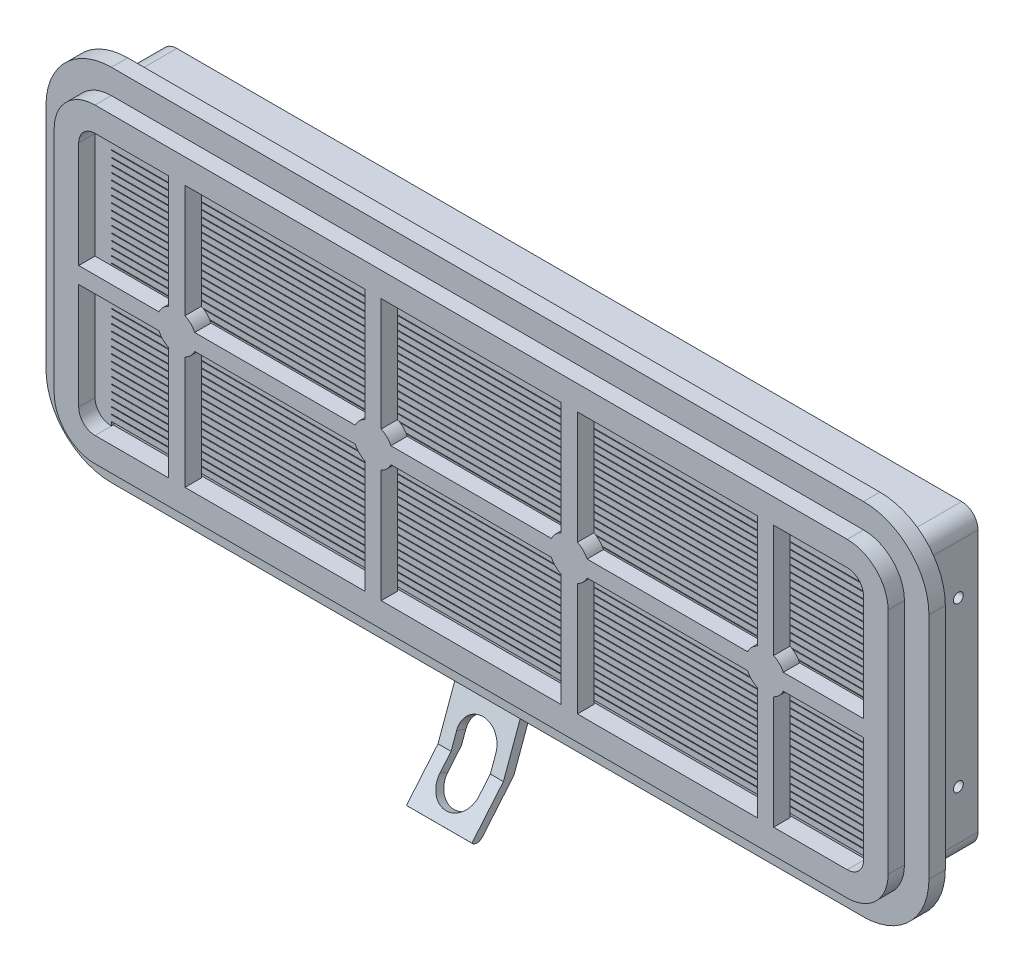
SolidWorks part; units mm, degrees
ref_plane "Plan de face" through (0, 0, 0) normal (0, 0, 1) x (1, 0, 0)
ref_plane "Plan de dessus" through (0, 0, 0) normal (0, 1, 0) x (1, 0, 0)
ref_plane "Plan de droite" through (0, 0, 0) normal (1, 0, 0) x (0, 0, -1)
sketch "Esquisse1" plane through (0, 0, 0) normal (0, 0, 1) x (1, 0, 0)
  line L0 (-115, 40) -> (115, 40)
  line L1 (-120, 45) -> (120, 45)
  line L2 (-125, 40) -> (-125, -40)
  line L3 (-120, -45) -> (120, -45)
  line L4 (125, 40) -> (125, -40)
  line L5 (-125, 45) -> (125, -45) construction
  line L6 (-125, -45) -> (125, 45) construction
  line L7 (120, 35) -> (120, -35)
  line L8 (-115, -40) -> (115, -40)
  line L9 (-120, 35) -> (-120, -35)
  line L10 (-125, -45) -> (125, -45) construction
  line L11 (125, 45) -> (125, -45) construction
  line L12 (120, 40) -> (120, -40) construction
  line L13 (-120, -40) -> (120, -40) construction
  line L14 (-125, 45) -> (125, 45) construction
  line L15 (-120, 40) -> (120, 40) construction
  line L16 (-120, 40) -> (-120, -40) construction
  line L17 (-125, 45) -> (-125, -45) construction
  arc A0 (120, -45) -> (125, -40) centre (120, -40) ccw
  arc A1 (120, -35) -> (115, -40) centre (115, -35) cw
  arc A2 (120, 45) -> (125, 40) centre (120, 40) cw
  arc A3 (115, 40) -> (120, 35) centre (115, 35) cw
  arc A4 (-115, -40) -> (-120, -35) centre (-115, -35) cw
  arc A5 (-125, -40) -> (-120, -45) centre (-120, -40) ccw
  arc A6 (-115, 40) -> (-120, 35) centre (-115, 35) ccw
  arc A7 (-120, 45) -> (-125, 40) centre (-120, 40) ccw
  point P0 (0, 0)
  dimension "D4" = 5
  dimension "D1" = 250
  dimension "D2" = 90
  dimension "D3" = 5
extrude "Boss.-Extru.1" add sketch "Esquisse1" along normal blind 50
sketch "Esquisse2" plane through (0, 0, 50) normal (0, 0, 1) x (1, 0, 0)
  line L0 (-115, -40) -> (115, -40) construction
  line L1 (120, -35) -> (120, 35) construction
  line L2 (115, 40) -> (-115, 40) construction
  line L3 (-120, 35) -> (-120, -35) construction
  line L4 (-115, -40) -> (115, -40)
  line L5 (120, -35) -> (120, 35)
  line L6 (115, 40) -> (-115, 40)
  line L7 (-120, 35) -> (-120, -35)
  line L8 (-115, -55) -> (115, -55)
  line L9 (135, -35) -> (135, 35)
  line L10 (115, 55) -> (-115, 55)
  line L11 (-135, 35) -> (-135, -35)
  arc A0 (-120, -35) -> (-115, -40) centre (-115, -35) ccw construction
  arc A1 (115, -40) -> (120, -35) centre (115, -35) ccw construction
  arc A2 (120, 35) -> (115, 40) centre (115, 35) ccw construction
  arc A3 (-115, 40) -> (-120, 35) centre (-115, 35) ccw construction
  arc A4 (-120, -35) -> (-115, -40) centre (-115, -35) ccw
  arc A5 (115, -40) -> (120, -35) centre (115, -35) ccw
  arc A6 (120, 35) -> (115, 40) centre (115, 35) ccw
  arc A7 (-115, 40) -> (-120, 35) centre (-115, 35) ccw
  arc A8 (-135, -35) -> (-115, -55) centre (-115, -35) ccw
  arc A9 (115, -55) -> (135, -35) centre (115, -35) ccw
  arc A10 (135, 35) -> (115, 55) centre (115, 35) ccw
  arc A11 (-115, 55) -> (-135, 35) centre (-115, 35) ccw
  dimension "D1" = 15
extrude "Boss.-Extru.3" add sketch "Esquisse2" along normal blind 5
sketch "Esquisse3" plane through (0, 0, 55) normal (0, 0, 1) x (1, 0, 0)
  line L0 (-120, 35) -> (-120, -35) construction
  line L1 (-120, 35) -> (-120, -35)
  line L2 (-115, -40) -> (115, -40) construction
  line L3 (120, -35) -> (120, 35) construction
  line L4 (115, 40) -> (-115, 40) construction
  line L5 (-115, -40) -> (115, -40)
  line L6 (120, -35) -> (120, 35)
  line L7 (115, 40) -> (-115, 40)
  line L8 (-127.5, 35) -> (-127.5, -35)
  line L9 (-115, -47.5) -> (115, -47.5)
  line L10 (127.5, -35) -> (127.5, 35)
  line L11 (115, 47.5) -> (-115, 47.5)
  arc A0 (-120, -35) -> (-115, -40) centre (-115, -35) ccw construction
  arc A1 (115, -40) -> (120, -35) centre (115, -35) ccw construction
  arc A2 (120, 35) -> (115, 40) centre (115, 35) ccw construction
  arc A3 (-115, 40) -> (-120, 35) centre (-115, 35) ccw construction
  arc A4 (-120, -35) -> (-115, -40) centre (-115, -35) ccw
  arc A5 (115, -40) -> (120, -35) centre (115, -35) ccw
  arc A6 (120, 35) -> (115, 40) centre (115, 35) ccw
  arc A7 (-115, 40) -> (-120, 35) centre (-115, 35) ccw
  arc A8 (-127.5, -35) -> (-115, -47.5) centre (-115, -35) ccw
  arc A9 (115, -47.5) -> (127.5, -35) centre (115, -35) ccw
  arc A10 (127.5, 35) -> (115, 47.5) centre (115, 35) ccw
  arc A11 (-115, 47.5) -> (-127.5, 35) centre (-115, 35) ccw
  dimension "D1" = 7.5
extrude "Boss.-Extru.4" add sketch "Esquisse3" along normal blind 5
sketch "Esquisse4" plane through (0, 0, 60) normal (0, 0, 1) x (1, 0, 0)
  line L0 (-180.9015, 0) -> (181.7643, 0) construction
  line L1 (-120, -2.5) -> (120, -2.5)
  line L2 (-120, 35) -> (-120, -35) construction
  line L3 (120, -35) -> (120, 35) construction
  line L4 (-127.5, 35) -> (-127.5, -35)
  line L5 (-115, -47.5) -> (115, -47.5)
  line L6 (127.5, -35) -> (127.5, 35)
  line L7 (115, 47.5) -> (-115, 47.5)
  line L8 (-127.5, 35) -> (-127.5, -35)
  line L9 (-115, -47.5) -> (115, -47.5)
  line L10 (127.5, -35) -> (127.5, 35)
  line L11 (115, 47.5) -> (-115, 47.5)
  line L12 (-120, 2.5) -> (120, 2.5)
  line L13 (-92.5, 40) -> (-92.5, -40)
  line L14 (-115, -40) -> (115, -40)
  line L15 (115, 40) -> (-115, 40)
  line L16 (-90, 75.1442) -> (-90, -69.1311) construction
  line L17 (115, 40) -> (-115, 40) construction
  line L18 (-115, -40) -> (115, -40) construction
  line L19 (-87.5, 40) -> (-87.5, -40)
  line L20 (-32.5, 40) -> (-32.5, -40)
  line L21 (-27.5, 40) -> (-27.5, -40)
  line L22 (27.5, 40) -> (27.5, -40)
  line L23 (32.5, 40) -> (32.5, -40)
  line L24 (87.5, 40) -> (87.5, -40)
  line L25 (92.5, 40) -> (92.5, -40)
  line L26 (120, -35) -> (120, 35)
  line L27 (-120, 35) -> (-120, -35)
  circle A0 centre (-90, 0) radius 6
  circle A1 centre (-30, 0) radius 6
  circle A2 centre (30, 0) radius 6
  circle A3 centre (90, 0) radius 6
  arc A4 (-115, 47.5) -> (-127.5, 35) centre (-115, 35) ccw
  arc A5 (-127.5, -35) -> (-115, -47.5) centre (-115, -35) ccw
  arc A6 (115, -47.5) -> (127.5, -35) centre (115, -35) ccw
  arc A7 (127.5, 35) -> (115, 47.5) centre (115, 35) ccw
  arc A8 (-115, 47.5) -> (-127.5, 35) centre (-115, 35) ccw
  arc A9 (-127.5, -35) -> (-115, -47.5) centre (-115, -35) ccw
  arc A10 (115, -47.5) -> (127.5, -35) centre (115, -35) ccw
  arc A11 (127.5, 35) -> (115, 47.5) centre (115, 35) ccw
  line M32 (-115, 40) -> (115, 40)
  dimension "D6" = 12
  dimension "D2" = 2.5
  dimension "D3" = 30
  dimension "D4" = 2.5
  dimension "D1" = 0
  dimension "D5" = 4
  dimension "D7" = 4
extrude "Boss.-Extru.5" add sketch "Esquisse4" against normal blind 5 contours A0 L19 L13 M32 | L19 A0 L13 L12 | L1 A0 L12 L19 | L12 A0 L19 | L19 L12 L13 L1 | L13 A0 L12 | L12 A0 L1 L13 | L13 A0 L19 L1 | L1 A0 L13 | L19 A0 L1 | A0 L13 L14 L19 region at (-94.1647, 0, 60) region at (-93.6011, -3.6011, 60) region at (-90, 0, 60) region at (-90, -4.1647, 60) region at (-93.6011, 3.6011, 60) region at (-90, -22.9104, 60) region at (-85.8353, 0, 60) region at (-86.3989, -3.6011, 60) region at (-90, 4.1647, 60) region at (-90, 22.9104, 60) region at (-86.3989, 3.6011, 60)
pattern_linear "Répétition linéaire1" count 4 spacing 60 along (1, 0, 0) of "Boss.-Extru.5"
sketch "Esquisse5" plane through (0, 0, 60) normal (0, 0, 1) x (1, 0, 0)
  line L0 (-163.933, 0) -> (179.1758, 0) construction
  line L1 (-120, 2.5) -> (120, 2.5)
  line L2 (-120, 35) -> (-120, -35) construction
  line L3 (120, -35) -> (120, 35) construction
  line L4 (-120, -2.5) -> (120, -2.5)
  line L5 (-120, 2.5) -> (-120, -2.5)
  line L6 (120, -2.5) -> (120, 2.5)
  dimension "D1" = 2.5
extrude "Boss.-Extru.6" add sketch "Esquisse5" against normal blind 5
sketch "Esquisse9" plane through (0, 0, 0) normal (1, 0, 0) x (0, 0, -1)
  line L0 (-55, -55) -> (-60.1303, -69.0954)
  line L1 (-55, -35) -> (-55, -55) construction
  line L2 (-51.596, -54.4191) -> (-56.9378, -69.0954)
  line L3 (-60.1303, -69.0954) -> (-69.7721, -80.5861)
  line L4 (-56.9378, -69.0954) -> (-66.5796, -80.5861)
  line L5 (-55, -55) -> (-51.596, -54.4191)
  arc A0 (-69.7721, -80.5861) -> (-66.5796, -80.5861) centre (-68.1758, -79.2466) ccw
  dimension "D1" = 15
  dimension "D2" = 160
  dimension "D3" = 3
  dimension "D4" = 160
  dimension "D5" = 15
extrude "Boss.-Extru.8" add sketch "Esquisse9" along normal blind 10 and the other way blind 10
ref_plane "Plan1" through (0, 14.6631, 40.2865) normal (0, 0.342, 0.9397) x (1, 0, 0)
sketch "Esquisse10" plane through (0, 14.6631, 40.2865) normal (0, 0.342, 0.9397) x (1, 0, 0)
  line L0 (-10, -85.4942) -> (10, -85.4942) construction
  line L1 (-10, -85.4942) -> (10, -85.4942)
  line L2 (0, -80.4942) -> (0, -90.4942) construction
  line L3 (6, -80.4942) -> (6, -90.4942)
  line L4 (-6, -80.4942) -> (-6, -90.4942)
  arc A0 (6, -80.4942) -> (-6, -80.4942) centre (0, -80.4942) ccw
  arc A1 (-6, -90.4942) -> (6, -90.4942) centre (0, -90.4942) ccw
  point P5 (0, -85.4942)
  dimension "D2" = 6
  dimension "D1" = 10
extrude "Enlèv. mat.-Extru.1" cut sketch "Esquisse10" against normal through all contours L3 A0 L4 L1 | L4 A1 L3 L1 region at (0, -61.0251, 67.8347) region at (0, -70.3253, 71.2197)
ref_plane "Plan2" through (115, 0, 0) normal (-1, 0, 0) x (0, 0, 1)
sketch "Esquisse11" plane through (115, 0, 0) normal (-1, 0, 0) x (0, 0, 1)
  line L0 (60, 35) -> (0, 35) construction
  line L1 (60, 35) -> (0, 35)
  line L2 (54.5087, 34.5001) -> (46.5299, 34.3608)
  line L3 (46.5299, 34.3608) -> (46.5299, 32.1863) construction
  line L4 (55.104, 34.1108) -> (42.39, 34.1108) construction
  line L5 (54.5087, 33.7216) -> (46.5299, 33.8609)
  line L6 (55, 35) -> (55, 33.2217)
  arc A0 (55, 35) -> (54.5087, 34.5001) centre (54.5, 35) cw
  arc A1 (46.5299, 34.3608) -> (46.5299, 33.8609) centre (46.5343, 34.1108) ccw
  arc A2 (55, 33.2217) -> (54.5087, 33.7216) centre (54.5, 33.2217) ccw
  dimension "D1" = 0.5
  dimension "D3" = 0.25
  dimension "D2" = 1
extrude "Boss.-Extru.9" add sketch "Esquisse11" along normal blind 230 contours A2 L6 A0 L2 A1 L5 region at (115, 34.1108, 51.0774)
pattern_linear "Répétition linéaire2" count 37 spacing 2 along (0, -1, 0) of "Boss.-Extru.9"
sketch "Esquisse12" plane through (-115, 0, 0) normal (-1, 0, 0) x (0, 0, 1)
  line L0 (55, -37) -> (55, -38.7783) construction
  line L1 (55, -37) -> (55, -38.7783)
  line L2 (55, 35) -> (55, 33.2217) construction
  line L3 (55, 35) -> (55, 33.2217)
  line L4 (60, -40) -> (0, -40) construction
  line L5 (60, -40) -> (40, -40)
  line L6 (60, 40) -> (0, 40) construction
  line L7 (60, 40) -> (40, 40)
  line L9 (60, -40) -> (40, -40)
  line L10 (60, -40) -> (60, 40)
  line L11 (60, 40) -> (40, 40)
  line L12 (40, -40) -> (40, 40)
  dimension "D1" = 20
extrude "Extru.-Mince1" add sketch "Esquisse12" along normal blind 5 thin contours L12 thin type one direction wall 10
sketch "Esquisse13" plane through (0, 0, 50) normal (0, 0, 1) x (1, 0, 0)
  line L76 (-120, 35) -> (-120, -35)
  line L77 (-115, -40) -> (-115, -38.1997)
  line L78 (-115, -38.1997) -> (-115, -37.5786)
  line L79 (-115, -37.5786) -> (-115, -36.1997)
  line L80 (-115, -36.1997) -> (-115, -35.5786)
  line L81 (-115, -35.5786) -> (-115, -34.1997)
  line L82 (-115, -34.1997) -> (-115, -33.5786)
  line L83 (-115, -33.5786) -> (-115, -32.1997)
  line L84 (-115, -32.1997) -> (-115, -31.5786)
  line L85 (-115, -31.5786) -> (-115, -30.1997)
  line L86 (-115, -30.1997) -> (-115, -29.5786)
  line L87 (-115, -29.5786) -> (-115, -28.1997)
  line L88 (-115, -28.1997) -> (-115, -27.5786)
  line L89 (-115, -27.5786) -> (-115, -26.1997)
  line L90 (-115, -26.1997) -> (-115, -25.5786)
  line L91 (-115, -25.5786) -> (-115, -24.1997)
  line L92 (-115, -24.1997) -> (-115, -23.5786)
  line L93 (-115, -23.5786) -> (-115, -22.1997)
  line L94 (-115, -22.1997) -> (-115, -21.5786)
  line L95 (-115, -21.5786) -> (-115, -20.1997)
  line L96 (-115, -20.1997) -> (-115, -19.5786)
  line L97 (-115, -19.5786) -> (-115, -18.1997)
  line L98 (-115, -18.1997) -> (-115, -17.5786)
  line L99 (-115, -17.5786) -> (-115, -16.1997)
  line L100 (-115, -16.1997) -> (-115, -15.5786)
  line L101 (-115, -15.5786) -> (-115, -14.1997)
  line L102 (-115, -14.1997) -> (-115, -13.5786)
  line L103 (-115, -13.5786) -> (-115, -12.1997)
  line L104 (-115, -12.1997) -> (-115, -11.5786)
  line L105 (-115, -11.5786) -> (-115, -10.1997)
  line L106 (-115, -10.1997) -> (-115, -9.5786)
  line L107 (-115, -9.5786) -> (-115, -8.1997)
  line L108 (-115, -8.1997) -> (-115, -7.5786)
  line L109 (-115, -7.5786) -> (-115, -6.1997)
  line L110 (-115, -6.1997) -> (-115, -5.5786)
  line L111 (-115, -5.5786) -> (-115, -4.1997)
  line L112 (-115, -4.1997) -> (-115, -3.5786)
  line L113 (-115, -3.5786) -> (-115, -2.1997)
  line L114 (-115, -2.1997) -> (-115, -1.5786)
  line L115 (-115, -1.5786) -> (-115, -0.1997)
  line L116 (-115, -0.1997) -> (-115, 0.4214)
  line L117 (-115, 0.4214) -> (-115, 1.8003)
  line L118 (-115, 1.8003) -> (-115, 2.4214)
  line L119 (-115, 2.4214) -> (-115, 3.8003)
  line L120 (-115, 3.8003) -> (-115, 4.4214)
  line L121 (-115, 4.4214) -> (-115, 5.8003)
  line L122 (-115, 5.8003) -> (-115, 6.4214)
  line L123 (-115, 6.4214) -> (-115, 7.8003)
  line L124 (-115, 7.8003) -> (-115, 8.4214)
  line L125 (-115, 8.4214) -> (-115, 9.8003)
  line L126 (-115, 9.8003) -> (-115, 10.4214)
  line L127 (-115, 10.4214) -> (-115, 11.8003)
  line L128 (-115, 11.8003) -> (-115, 12.4214)
  line L129 (-115, 12.4214) -> (-115, 13.8003)
  line L130 (-115, 13.8003) -> (-115, 14.4214)
  line L131 (-115, 14.4214) -> (-115, 15.8003)
  line L132 (-115, 15.8003) -> (-115, 16.4214)
  line L133 (-115, 16.4214) -> (-115, 17.8003)
  line L134 (-115, 17.8003) -> (-115, 18.4214)
  line L135 (-115, 18.4214) -> (-115, 19.8003)
  line L136 (-115, 19.8003) -> (-115, 20.4214)
  line L137 (-115, 20.4214) -> (-115, 21.8003)
  line L138 (-115, 21.8003) -> (-115, 22.4214)
  line L139 (-115, 22.4214) -> (-115, 23.8003)
  line L140 (-115, 23.8003) -> (-115, 24.4214)
  line L141 (-115, 24.4214) -> (-115, 25.8003)
  line L142 (-115, 25.8003) -> (-115, 26.4214)
  line L143 (-115, 26.4214) -> (-115, 27.8003)
  line L144 (-115, 27.8003) -> (-115, 28.4214)
  line L145 (-115, 28.4214) -> (-115, 29.8003)
  line L146 (-115, 29.8003) -> (-115, 30.4214)
  line L147 (-115, 30.4214) -> (-115, 31.8003)
  line L148 (-115, 31.8003) -> (-115, 32.4214)
  line L149 (-115, 32.4214) -> (-115, 33.8003)
  line L150 (-115, 33.8003) -> (-115, 34.4214)
  line L151 (-115, 34.4214) -> (-115, 40)
  line L152 (-120, 35) -> (-120, -35)
  line L153 (-115, -40) -> (-115, -38.1997)
  line L154 (-115, -38.1997) -> (-115, -37.5786)
  line L155 (-115, -37.5786) -> (-115, -36.1997)
  line L156 (-115, -36.1997) -> (-115, -35.5786)
  line L157 (-115, -35.5786) -> (-115, -34.1997)
  line L158 (-115, -34.1997) -> (-115, -33.5786)
  line L159 (-115, -33.5786) -> (-115, -32.1997)
  line L160 (-115, -32.1997) -> (-115, -31.5786)
  line L161 (-115, -31.5786) -> (-115, -30.1997)
  line L162 (-115, -30.1997) -> (-115, -29.5786)
  line L163 (-115, -29.5786) -> (-115, -28.1997)
  line L164 (-115, -28.1997) -> (-115, -27.5786)
  line L165 (-115, -27.5786) -> (-115, -26.1997)
  line L166 (-115, -26.1997) -> (-115, -25.5786)
  line L167 (-115, -25.5786) -> (-115, -24.1997)
  line L168 (-115, -24.1997) -> (-115, -23.5786)
  line L169 (-115, -23.5786) -> (-115, -22.1997)
  line L170 (-115, -22.1997) -> (-115, -21.5786)
  line L171 (-115, -21.5786) -> (-115, -20.1997)
  line L172 (-115, -20.1997) -> (-115, -19.5786)
  line L173 (-115, -19.5786) -> (-115, -18.1997)
  line L174 (-115, -18.1997) -> (-115, -17.5786)
  line L175 (-115, -17.5786) -> (-115, -16.1997)
  line L176 (-115, -16.1997) -> (-115, -15.5786)
  line L177 (-115, -15.5786) -> (-115, -14.1997)
  line L178 (-115, -14.1997) -> (-115, -13.5786)
  line L179 (-115, -13.5786) -> (-115, -12.1997)
  line L180 (-115, -12.1997) -> (-115, -11.5786)
  line L181 (-115, -11.5786) -> (-115, -10.1997)
  line L182 (-115, -10.1997) -> (-115, -9.5786)
  line L183 (-115, -9.5786) -> (-115, -8.1997)
  line L184 (-115, -8.1997) -> (-115, -7.5786)
  line L185 (-115, -7.5786) -> (-115, -6.1997)
  line L186 (-115, -6.1997) -> (-115, -5.5786)
  line L187 (-115, -5.5786) -> (-115, -4.1997)
  line L188 (-115, -4.1997) -> (-115, -3.5786)
  line L189 (-115, -3.5786) -> (-115, -2.1997)
  line L190 (-115, -2.1997) -> (-115, -1.5786)
  line L191 (-115, -1.5786) -> (-115, -0.1997)
  line L192 (-115, -0.1997) -> (-115, 0.4214)
  line L193 (-115, 0.4214) -> (-115, 1.8003)
  line L194 (-115, 1.8003) -> (-115, 2.4214)
  line L195 (-115, 2.4214) -> (-115, 3.8003)
  line L196 (-115, 3.8003) -> (-115, 4.4214)
  line L197 (-115, 4.4214) -> (-115, 5.8003)
  line L198 (-115, 5.8003) -> (-115, 6.4214)
  line L199 (-115, 6.4214) -> (-115, 7.8003)
  line L200 (-115, 7.8003) -> (-115, 8.4214)
  line L201 (-115, 8.4214) -> (-115, 9.8003)
  line L202 (-115, 9.8003) -> (-115, 10.4214)
  line L203 (-115, 10.4214) -> (-115, 11.8003)
  line L204 (-115, 11.8003) -> (-115, 12.4214)
  line L205 (-115, 12.4214) -> (-115, 13.8003)
  line L206 (-115, 13.8003) -> (-115, 14.4214)
  line L207 (-115, 14.4214) -> (-115, 15.8003)
  line L208 (-115, 15.8003) -> (-115, 16.4214)
  line L209 (-115, 16.4214) -> (-115, 17.8003)
  line L210 (-115, 17.8003) -> (-115, 18.4214)
  line L211 (-115, 18.4214) -> (-115, 19.8003)
  line L212 (-115, 19.8003) -> (-115, 20.4214)
  line L213 (-115, 20.4214) -> (-115, 21.8003)
  line L214 (-115, 21.8003) -> (-115, 22.4214)
  line L215 (-115, 22.4214) -> (-115, 23.8003)
  line L216 (-115, 23.8003) -> (-115, 24.4214)
  line L217 (-115, 24.4214) -> (-115, 25.8003)
  line L218 (-115, 25.8003) -> (-115, 26.4214)
  line L219 (-115, 26.4214) -> (-115, 27.8003)
  line L220 (-115, 27.8003) -> (-115, 28.4214)
  line L221 (-115, 28.4214) -> (-115, 29.8003)
  line L222 (-115, 29.8003) -> (-115, 30.4214)
  line L223 (-115, 30.4214) -> (-115, 31.8003)
  line L224 (-115, 31.8003) -> (-115, 32.4214)
  line L225 (-115, 32.4214) -> (-115, 33.8003)
  line L226 (-115, 33.8003) -> (-115, 34.4214)
  line L227 (-115, 34.4214) -> (-115, 40)
  arc A2 (-115, 40) -> (-120, 35) centre (-115, 35) ccw
  arc A3 (-120, -35) -> (-115, -40) centre (-115, -35) ccw
  arc A4 (-115, 40) -> (-120, 35) centre (-115, 35) ccw
  arc A5 (-120, -35) -> (-115, -40) centre (-115, -35) ccw
  dimension "D1" = 0
extrude "Boss.-Extru.13" add sketch "Esquisse13" along normal blind 5
mirror "Symétrie1" about plane through (0, 0, 0) normal (1, 0, 0) of "Extru.-Mince1"
mirror "Symétrie2" about plane through (0, 0, 0) normal (1, 0, 0) of "Boss.-Extru.13"
sketch "Esquisse14" plane through (0, 33.5384, -0.5854) normal (0, 0.9998, -0.0175) x (1, 0, 0)
  line L0 (115, 22) -> (115, -22) construction
  line L1 (-115, -55.1025) -> (115, -55.1025)
  line L2 (-115, -55.1025) -> (-115, -35.1025)
  line L3 (-115, -35.1025) -> (115, -35.1025)
  line L4 (115, -55.1025) -> (115, -47.1225)
  line L5 (115, -47.1225) -> (-115, -47.1225)
  line L6 (-115, -47.1225) -> (-115, -55.1025)
  line L7 (-115, -55.1025) -> (115, -55.1025)
  line L8 (115, -55.1025) -> (115, -47.1225)
  line L10 (-115, -47.1225) -> (-115, -55.1025)
  line L11 (-115, -55.1025) -> (115, -55.1025)
  line L12 (115, -55.1025) -> (115, -35.1025)
  line M5 (115, -55.1025) -> (115, -47.1225)
  line M6 (115, -47.1225) -> (-115, -47.1225)
  line M7 (-115, -47.1225) -> (-115, -55.1025)
  line M8 (-115, -55.1025) -> (115, -55.1025)
  dimension "D2" = 20
  dimension "D1" = 0
extrude "Boss.-Extru.14" add sketch "Esquisse14" along normal blind 5.75 contours M8 M5 M6 M7 region at (0, 34.4304, 50.5193)
mirror "Symétrie3" about plane through (0, 0, 0) normal (0, 1, 0) of "Boss.-Extru.14"
sketch "Esquisse15" plane through (0, 0, 0) normal (0, 0, -1) x (-1, 0, 0)
  line L0 (-115, -40) -> (115, -40) construction
  line L1 (120, -35) -> (120, 35) construction
  line L2 (-115, 40) -> (115, 40) construction
  line L3 (-120, -35) -> (-120, 35) construction
  line L4 (-120, -45) -> (120, -45)
  line L5 (125, -40) -> (125, 40)
  line L6 (120, 45) -> (-120, 45)
  line L7 (-125, 40) -> (-125, -40)
  line L8 (-120, -45) -> (120, -45)
  line L9 (125, -40) -> (125, 40)
  line L10 (120, 45) -> (-120, 45)
  line L11 (-125, 40) -> (-125, -40)
  line L12 (-115, -40) -> (115, -40)
  line L13 (120, -35) -> (120, 35)
  line L14 (-115, 40) -> (115, 40)
  line L15 (-120, -35) -> (-120, 35)
  arc A0 (-120, -35) -> (-115, -40) centre (-115, -35) ccw construction
  arc A1 (115, -40) -> (120, -35) centre (115, -35) ccw construction
  arc A2 (120, 35) -> (115, 40) centre (115, 35) ccw construction
  arc A3 (-115, 40) -> (-120, 35) centre (-115, 35) ccw construction
  arc A4 (-125, -40) -> (-120, -45) centre (-120, -40) ccw
  arc A5 (120, -45) -> (125, -40) centre (120, -40) ccw
  arc A6 (125, 40) -> (120, 45) centre (120, 40) ccw
  arc A7 (-120, 45) -> (-125, 40) centre (-120, 40) ccw
  arc A8 (-125, -40) -> (-120, -45) centre (-120, -40) ccw
  arc A9 (120, -45) -> (125, -40) centre (120, -40) ccw
  arc A10 (125, 40) -> (120, 45) centre (120, 40) ccw
  arc A11 (-120, 45) -> (-125, 40) centre (-120, 40) ccw
  arc A12 (-120, -35) -> (-115, -40) centre (-115, -35) ccw
  arc A13 (115, -40) -> (120, -35) centre (115, -35) ccw
  arc A14 (120, 35) -> (115, 40) centre (115, 35) ccw
  arc A15 (-115, 40) -> (-120, 35) centre (-115, 35) ccw
  dimension "D1" = 0
extrude "Enlèv. mat.-Extru.2" cut sketch "Esquisse15" against normal blind 30
sketch "Esquisse16" plane through (125, 0, 0) normal (1, 0, 0) x (0, 0, -1)
  circle A0 centre (-36, 25) radius 1.5
  circle A1 centre (-36, -25) radius 1.5
  dimension "D1" = 3
  dimension "D2" = 3
extrude "Enlèv. mat.-Extru.3" cut sketch "Esquisse16" against normal through all
sketch "Esquisse17" plane through (0, 0, 60) normal (0, 0, 1) x (1, 0, 0)
  line L6 (-115, -55) -> (-10, -55)
  line L7 (-10, -55) -> (10, -55)
  line L8 (10, -55) -> (115, -55)
  line L9 (135, -35) -> (135, 35)
  line L10 (115, 55) -> (-115, 55)
  line L11 (-135, 35) -> (-135, -35)
  line L12 (-115, -55) -> (-10, -55)
  line L13 (-10, -55) -> (10, -55)
  line L14 (10, -55) -> (115, -55)
  line L15 (135, -35) -> (135, 35)
  line L16 (115, 55) -> (-115, 55)
  line L17 (-135, 35) -> (-135, -35)
  arc A4 (-135, -35) -> (-115, -55) centre (-115, -35) ccw
  arc A5 (115, -55) -> (135, -35) centre (115, -35) ccw
  arc A6 (135, 35) -> (115, 55) centre (115, 35) ccw
  arc A7 (-115, 55) -> (-135, 35) centre (-115, 35) ccw
  arc A8 (-135, -35) -> (-115, -55) centre (-115, -35) ccw
  arc A9 (115, -55) -> (135, -35) centre (115, -35) ccw
  arc A10 (135, 35) -> (115, 55) centre (115, 35) ccw
  arc A11 (-115, 55) -> (-135, 35) centre (-115, 35) ccw
  dimension "D1" = 0
